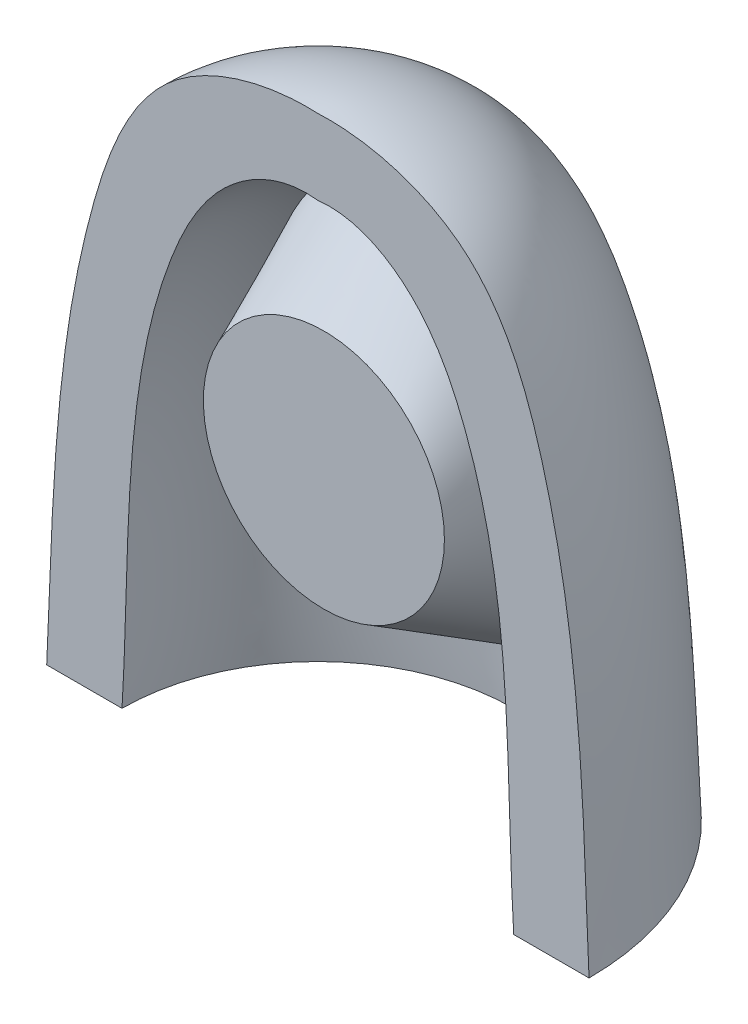
SolidWorks part; units mm, degrees
ref_plane "Plan de face" through (0, 0, 0) normal (0, 0, 1) x (1, 0, 0)
ref_plane "Plan de dessus" through (0, 0, 0) normal (0, 1, 0) x (1, 0, 0)
ref_plane "Plan de droite" through (0, 0, 0) normal (1, 0, 0) x (0, 0, -1)
sketch "Sketch1" plane through (0, 0, 0) normal (0, 0, 1) x (1, 0, 0)
  line L0 (0, 24.0802) -> (0, -22.399) construction
  line L1 (-32.5945, 0) -> (42.86, 0) construction
  line L2 (6.5, 0) -> (9, 0)
  line L3 (0, 20.35) -> (0, 17.85)
  spline S0 degree 3 poles (0, 20.35) (1.676, 20.4282) (5.6604, 19.3725) (8.7405, 10.942) (8.7941, 4.7856) (9, 0) knots 0 0 0 0 0.209087 0.440429 1 1 1 1
  spline S1 degree 3 poles (0, 17.85) (1.2485, 18.0031) (3.4343, 16.8333) (6.6173, 10.5141) (6.2204, 4.5323) (6.5, 0) knots 0 0 0 0 0.174731 0.328982 1 1 1 1
  dimension "D1" = 17.85
  dimension "D2" = 2.5
  dimension "D3" = 2.5
  dimension "D4" = 9
revolve "Revolve1" add sketch "Sketch1" angle 360 about L0
ref_plane "Plane1" through (0, 0, 9) normal (0, 0, 1) x (1, 0, 0)
sketch "Sketch2" plane through (0, 0, 9) normal (0, 0, 1) x (1, 0, 0)
  line L1 (10.8208, 22.0779) -> (-11.0993, 22.0779)
  line L2 (10.8208, 22.0779) -> (10.8208, -0.837)
  line L3 (10.8208, -0.837) -> (-11.0993, -0.837)
  line L4 (-11.0993, 22.0779) -> (-11.0993, -0.837)
extrude "Cut-Extrude1" cut sketch "Sketch2" against normal blind 9
ref_plane "Plane2" through (0, 0, -6.5) normal (0, 0, 1) x (1, 0, 0)
sketch "Sketch3" plane through (0, 0, -6.5) normal (0, 0, 1) x (1, 0, 0)
  line L0 (-9.6453, 7.7225) -> (10.7258, 7.7225) construction
ref_plane "Plane3" through (0, 1.3444, -7.6246) normal (0, -0.1736, 0.9848) x (1, 0, 0)
sketch "Sketch5" plane through (0, 1.3444, -7.6246) normal (0, -0.1736, 0.9848) x (1, 0, 0)
  line L0 (0, 0) -> (0, 18.0317) construction
  ellipse E0 centre (0, 8.9295) end of major axis (0, 0) minor radius 5.392
ref_plane "Plane4" through (0, 0, -0.2) normal (0, 0, 1) x (1, 0, 0)
sketch "Sketch6" plane through (0, 0, -0.2) normal (0, 0, 1) x (1, 0, 0)
  circle A0 centre (0, 10) radius 4
  dimension "D2" = 8
  dimension "D1" = 10
loft "Loft1" add profiles "Sketch5", "Sketch6" connector at (0, 1.3444, -7.6246) connector at (0.0127, 6, -0.2)
